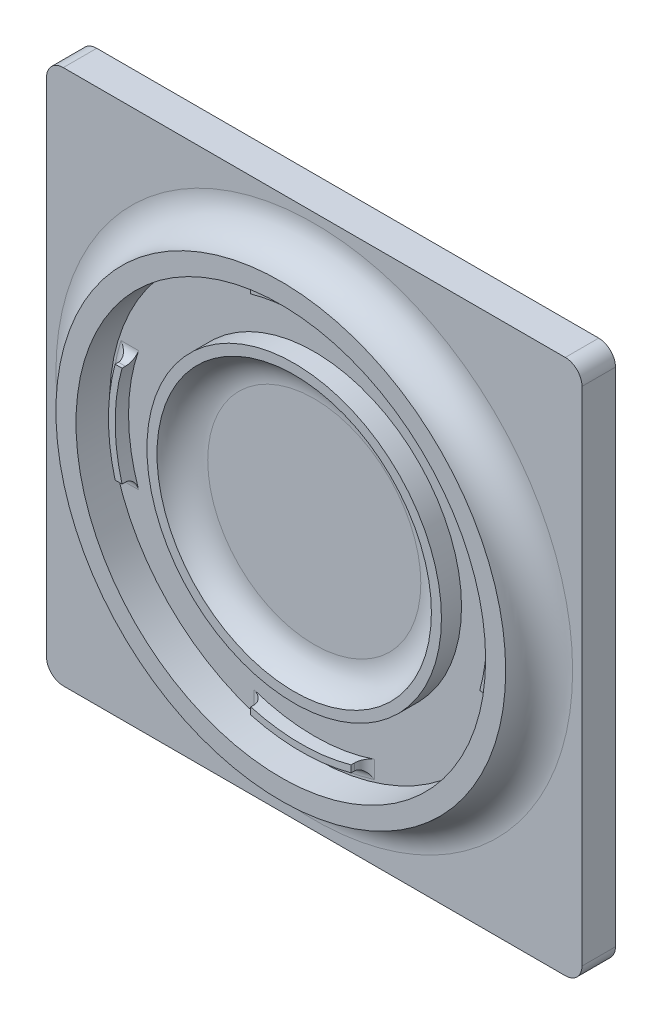
SolidWorks part; units mm, degrees
ref_plane "Front Plane" through (0, 0, 0) normal (0, 0, 1) x (1, 0, 0)
ref_plane "Top Plane" through (0, 0, 0) normal (0, 1, 0) x (1, 0, 0)
ref_plane "Right Plane" through (0, 0, 0) normal (1, 0, 0) x (0, 0, -1)
sketch "Sketch1" plane through (0, 0, 0) normal (0, 0, 1) x (1, 0, 0)
  line L1 (-40, 40) -> (40, 40)
  line L2 (-40, 40) -> (-40, -40)
  line L3 (-40, -40) -> (40, -40)
  line L4 (40, 40) -> (40, -40)
  line L5 (-40, 40) -> (40, -40) construction
  line L6 (-40, -40) -> (40, 40) construction
  point P0 (0, 0)
  dimension "D1" = 80
  dimension "D2" = 80
extrude "Boss-Extrude1" add sketch "Sketch1" along normal blind 5
fillet "Fillet1" radius 2.5 4 edges at (40, 40, 2.5) (-40, 40, 2.5) (40, -40, 2.5) (-40, -40, 2.5)
sketch "Sketch5" plane through (0, 0, 5) normal (0, 0, 1) x (1, 0, 0)
  line L5 (0, 29) -> (0, 27.75) construction
  line L6 (-7.5, 29) -> (7.5, 29)
  line L11 (-7.5, 29) -> (-7.5, -29)
  line L12 (-7.5, -29) -> (7.5, -29)
  line L16 (7.5, 29) -> (7.5, -29)
  line L17 (-7.5, 29) -> (7.5, -29) construction
  line L18 (-7.5, -29) -> (7.5, 29) construction
  line L19 (-29, 7.5) -> (29, 7.5)
  line L20 (-29, 7.5) -> (-29, -7.5)
  line L21 (-29, -7.5) -> (29, -7.5)
  line L22 (29, 7.5) -> (29, -7.5)
  line L23 (-29, 7.5) -> (29, -7.5) construction
  line L24 (-29, -7.5) -> (29, 7.5) construction
  line L26 (-2, 29.0722) -> (2, 29.0722)
  line L27 (-2, 29.0722) -> (-2, 27.6778)
  line L28 (-2, 27.6778) -> (2, 27.6778)
  line L29 (2, 29.0722) -> (2, 27.6778)
  line L30 (-2, 29.0722) -> (2, 27.6778) construction
  line L31 (-2, 27.6778) -> (2, 29.0722) construction
  circle A8 centre (0, 0) radius 27.75
  circle A9 centre (0, 0) radius 28.75
  point P14 (0, 28.375)
  dimension "D1" = 57.5
  dimension "D2" = 55.5
  dimension "D3" = 15
  dimension "D4" = 58
  dimension "D5" = 15
  dimension "D6" = 58
  dimension "D7" = 4
extrude "Boss-Extrude5" add sketch "Sketch5" along normal blind 2 contours L19 A9 L21 A8 | L27 A9 L11 A8 | L16 A9 L29 A8 | A9 L19 A8 L21 | L11 A9 L16 A8 region at (-4.7656, 27.7983, 5) region at (-27.9111, 0, 5) region at (4.7656, 27.7983, 5) region at (0, -27.9111, 5) region at (27.9111, 0, 5)
sketch "Sketch12" plane through (0, 0, 5) normal (0, 0, 1) x (1, 0, 0)
  circle A0 centre (0, 0) radius 30.6
  circle A1 centre (0, 0) radius 33.6
  dimension "D1" = 61.2
  dimension "D2" = 67.2
extrude "Boss-Extrude8" add sketch "Sketch12" along normal blind 5
sketch "Sketch13" plane through (0, 0, 5) normal (0, 0, 1) x (1, 0, 0)
  circle A0 centre (0, 0) radius 20.5
  circle A1 centre (0, 0) radius 22
  dimension "D1" = 44
  dimension "D2" = 41
extrude "Boss-Extrude9" add sketch "Sketch13" along normal blind 3
fillet "Fillet2" radius 1.5 15 edges at (28.75, 0, 5) (0, -28.75, 5) (-28.75, 0, 5) (4.7725, 28.3511, 5) (-4.7725, 28.3511, 5) (7.5, -27.2359, 5) (-7.5, -27.2359, 5) (-27.2359, -7.5, 5) (-27.2359, 7.5, 5) (27.2359, 7.5, 5) (27.2359, -7.5, 5) (7.5, 27.2359, 5) (2, 28.1791, 5) (-2, 28.1791, 5) (-7.5, 27.2359, 5)
fillet "Fillet3" radius 5 2 edges at (33.6, 0, 5) (20.5, 0, 5)
